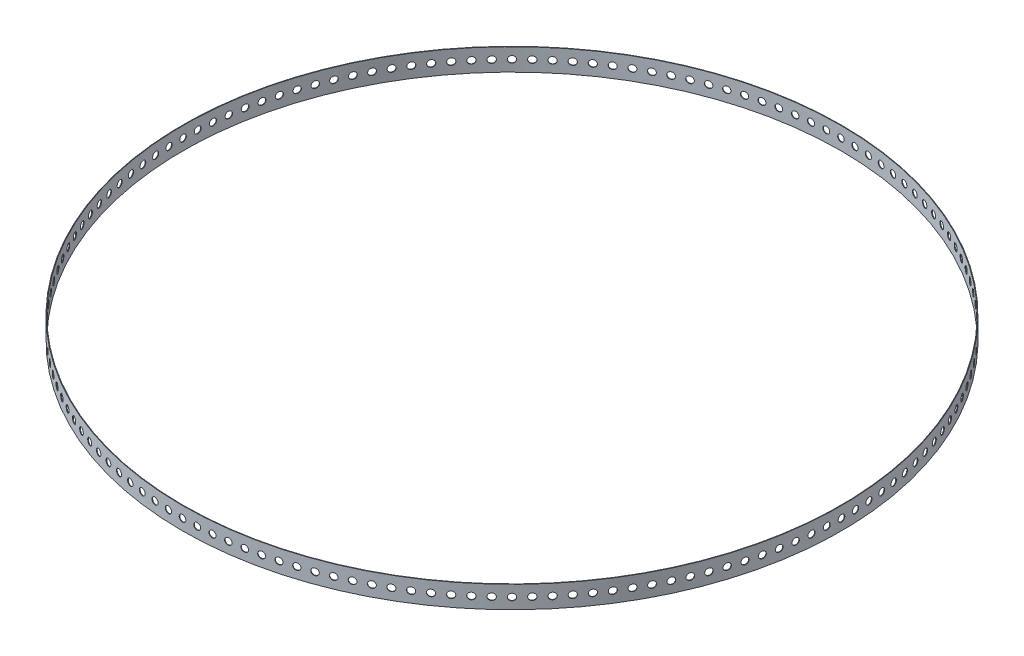
SolidWorks part; units mm, degrees
ref_plane "Front Plane" through (0, 0, 0) normal (0, 0, 1) x (1, 0, 0)
ref_plane "Top Plane" through (0, 0, 0) normal (0, 1, 0) x (1, 0, 0)
ref_plane "Right Plane" through (0, 0, 0) normal (1, 0, 0) x (0, 0, -1)
sketch "Sketch1" plane through (0, 0, 0) normal (0, 1, 0) x (1, 0, 0)
  circle A0 centre (0, 0) radius 299.5
  circle A1 centre (0, 0) radius 299
  dimension "D1" = 599
  dimension "D2" = 0.5
extrude "Boss-Extrude1" add sketch "Sketch1" along normal mid plane 20
sketch "Sketch2" plane through (0, 0, 0) normal (0, 0, 1) x (1, 0, 0)
  circle A0 centre (0, 0) radius 3
  dimension "D1" = 6
extrude "Cut-Extrude1" cut sketch "Sketch2" against normal through all
pattern_circular "CirPattern1" count 144 over 360 about axis through (0, 10, 0) along (0, -1, 0) of "Cut-Extrude1"
